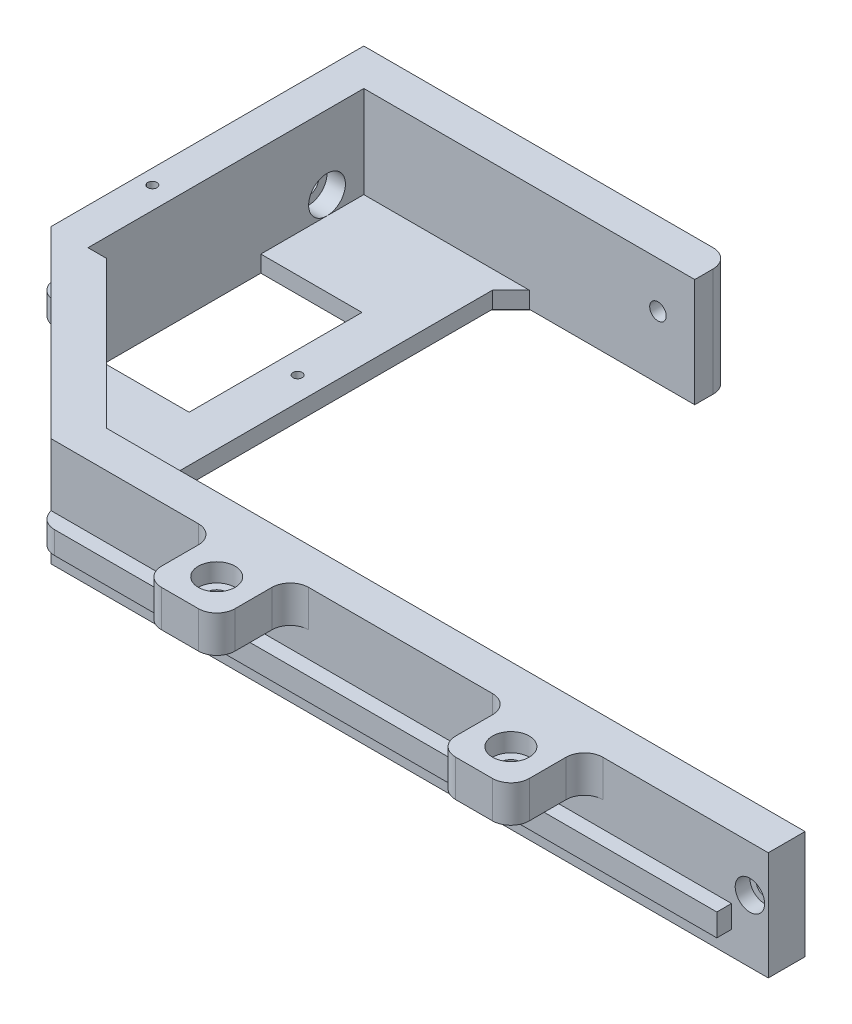
SolidWorks part; units mm, degrees
ref_plane "Front Plane" through (0, 0, 0) normal (0, 0, 1) x (1, 0, 0)
ref_plane "Top Plane" through (0, 0, 0) normal (0, 1, 0) x (1, 0, 0)
ref_plane "Right Plane" through (0, 0, 0) normal (1, 0, 0) x (0, 0, -1)
sketch "Sketch1" plane through (0, 0, 0) normal (0, 1, 0) x (1, 0, 0)
  line L0 (245, 10) -> (50, 10)
  line L1 (0, 0) -> (245, 0)
  line L2 (0, 0) -> (0, 135)
  line L3 (0, 135) -> (100, 135)
  line L4 (245, 0) -> (245, 10)
  line L5 (50, 10) -> (50, 125)
  line L6 (50, 125) -> (100, 125)
  line L7 (100, 125) -> (100, 135)
  dimension "D1" = 245
  dimension "D2" = 135
  dimension "D3" = 10
  dimension "D4" = 50
  dimension "D5" = 50
extrude "Boss-Extrude1" add sketch "Sketch1" along normal blind 30
sketch "Sketch3" plane through (0, 0, 0) normal (0, -1, 0) x (1, 0, 0)
  line L0 (50, 0) -> (0, -50)
  line L1 (0, 0) -> (245, 0) construction
  line L2 (0, -135) -> (0, 0) construction
  line L3 (0, -50) -> (0, 0)
  line L4 (0, 0) -> (50, 0)
  dimension "D1" = 45
  dimension "D2" = 50
extrude "Cut-Extrude1" cut sketch "Sketch3" against normal through all
chamfer "Chamfer1" distance 5 angle 45 2 edges at (50, 15, -125) (50, 15, -10)
sketch "Sketch4" plane through (0, 0, -135) normal (0, 0, -1) x (-1, 0, 0)
  arc A0 (-90, 15.5) -> (-90, 19.5) centre (-90, 17.5) ccw construction
  arc A1 (-90, 15.5) -> (-90, 19.5) centre (-90, 17.5) ccw
sketch "Sketch5" plane through (0, 0, 0) normal (0, 0, 1) x (1, 0, 0)
  arc A0 (240, 19.5) -> (240, 15.5) centre (240, 17.5) ccw construction
  arc A1 (90, 19.5) -> (90, 15.5) centre (90, 17.5) ccw construction
  arc A2 (240, 19.5) -> (240, 15.5) centre (240, 17.5) ccw
  arc A3 (90, 19.5) -> (90, 15.5) centre (90, 17.5) ccw
hole_wizard "CBORE for M4 SHCS2" positions "Sketch6" profile "Sketch7" counterbore size "M4" standard "ANSI Metric" end condition through all
sketch "Sketch6" plane through (0, 0, 0) normal (0, 0, 1) x (1, 0, 0)
  point P0 (240, 17.5)
  point P2 (90, 17.5)
sketch "Sketch7" plane through (240, 17.5, 0) normal (1, 0, 0) x (0, -1, 0)
  line L0 (0, 0) -> (0, 135)
  line L1 (0, 135) -> (2.25, 135)
  line L3 (2.25, 135) -> (2.25, 4)
  line L4 (2.25, 4) -> (4, 4)
  line L5 (4, 4) -> (4, 0)
  line L7 (4, 0) -> (0, 0)
  line L11 (0, -6.35) -> (0, 107.95) construction
  dimension "Thru Hole Dia." = 4.5
  dimension "Thru Hole Depth" = 135
  dimension "C'Bore Dia." = 8
  dimension "C'Bore Depth" = 4
hole_wizard "CBORE for M4 SHCS1" positions "Sketch8" profile "Sketch9" counterbore size "M4" standard "ANSI Metric" end condition through all
sketch "Sketch8" plane through (0, 0, -135) normal (0, 0, -1) x (-1, 0, 0)
  point P0 (-90, 17.5)
sketch "Sketch9" plane through (90, 17.5, -135) normal (1, 0, 0) x (0, 1, 0)
  line L0 (0, 0) -> (0, 135)
  line L1 (0, 135) -> (2.25, 135)
  line L3 (2.25, 135) -> (2.25, 4)
  line L4 (2.25, 4) -> (4, 4)
  line L5 (4, 4) -> (4, 0)
  line L7 (4, 0) -> (0, 0)
  line L11 (0, -6.35) -> (0, 107.95) construction
  dimension "Thru Hole Dia." = 4.5
  dimension "Thru Hole Depth" = 135
  dimension "C'Bore Dia." = 8
  dimension "C'Bore Depth" = 4
sketch "Sketch10" plane through (0, 30, 0) normal (0, 1, 0) x (1, 0, 0)
  line L0 (55, 125) -> (10, 125)
  line L1 (10, 125) -> (10, 55)
  line L2 (10, 55) -> (50, 15)
  line L3 (50, 15) -> (55, 125)
  line L4 (55, 10) -> (50, 15) construction
  line L5 (0, 135) -> (0, 50) construction
  dimension "D1" = 10
extrude "Cut-Extrude2" cut sketch "Sketch10" against normal offset from surface (25 mm away) 5 up to face at (86.3636, 0, -65.9091)
sketch "Sketch11" plane through (0, 30, 0) normal (0, 1, 0) x (1, 0, 0)
  line L0 (10, 125) -> (10, 55) construction
  line L1 (10, 50) -> (37.5, 50)
  line L2 (10, 50) -> (10, 97)
  line L3 (10, 97) -> (37.5, 97)
  line L4 (37.5, 50) -> (37.5, 97)
  dimension "D1" = 5
  dimension "D2" = 27.5
  dimension "D3" = 47
extrude "Cut-Extrude3" cut sketch "Sketch11" against normal through all
sketch "Sketch15" plane through (10, 0, 0) normal (1, 0, 0) x (0, 0, -1)
  line L0 (125, 10) -> (115, 10)
  line L1 (125, 5) -> (125, 30) construction
  line L2 (15, 0) -> (120, 0) construction
  dimension "D1" = 10
  dimension "D2" = 10
hole_wizard "CBORE for M5 SHCS2" positions "Sketch16" profile "Sketch17" counterbore size "M5" standard "ANSI Metric" end condition through all
sketch "Sketch16" plane through (10, 0, 0) normal (1, 0, 0) x (0, 0, -1)
  point P0 (115, 10)
sketch "Sketch17" plane through (10, 10, -115) normal (0, 1, 0) x (0, 0, -1)
  line L0 (0, 0) -> (0, 10)
  line L1 (0, 10) -> (2.75, 10)
  line L3 (2.75, 10) -> (2.75, 5)
  line L4 (2.75, 5) -> (5, 5)
  line L5 (5, 5) -> (5, 0)
  line L7 (5, 0) -> (0, 0)
  line L11 (0, -6.35) -> (0, 107.95) construction
  dimension "Thru Hole Dia." = 5.5
  dimension "Thru Hole Depth" = 10
  dimension "C'Bore Dia." = 10
  dimension "C'Bore Depth" = 5
sketch "Sketch18" plane through (0, 0, 0) normal (0, -1, 0) x (1, 0, 0)
  circle A0 centre (43.5, -73.5) radius 1.5 construction
  circle A1 centre (4, -73.5) radius 1.5 construction
  circle A2 centre (43.5, -73.5) radius 1.5
  circle A3 centre (4, -73.5) radius 1.5
hole_wizard "M3x0.5 Tapped Hole1" positions "Sketch19" profile "Sketch20" tap size "M3x0.5" standard "ANSI Metric" end condition through all
sketch "Sketch19" plane through (0, 0, 0) normal (0, -1, 0) x (-1, 0, 0)
  point P0 (-4, 73.5)
  point P3 (-43.5, 73.5)
sketch "Sketch20" plane through (4, 0, -73.5) normal (1, 0, 0) x (0, 0, -1)
  line L0 (0, 0) -> (0, 30)
  line L1 (0, 30) -> (1.25, 30)
  line L2 (1.25, 30) -> (1.25, 0)
  line L5 (1.25, 0) -> (0, 0)
  line L11 (0, -6.35) -> (0, 107.95) construction
  dimension "Thru Tap Drill Dia." = 2.5
  dimension "Thru Tap Drill Depth" = 30
cosmetic thread "Hole Thread1" parameters "D2"=3
cosmetic thread "Hole Thread2" parameters "D2"=3
sketch "Sketch21" plane through (0, 0, 0) normal (0, 0, 1) x (1, 0, 0)
  line L0 (50, 30) -> (50, 0) construction
  line L1 (50, 13.05) -> (235, 13.05)
  line L2 (50, 13.05) -> (50, 6.95)
  line L3 (50, 6.95) -> (235, 6.95)
  line L4 (235, 13.05) -> (235, 6.95)
  line L5 (245, 10) -> (235, 10) construction
  line L6 (245, 30) -> (245, 0) construction
  line L7 (50, 0) -> (245, 0) construction
  dimension "D1" = 6.1
  dimension "D2" = 10
  dimension "D3" = 10
extrude "Boss-Extrude3" add sketch "Sketch21" along normal blind 4
sketch "Sketch22" plane through (0, 0, 0) normal (-1, 0, 0) x (0, 0, 1)
  line L0 (-50, 30) -> (-50, 0) construction
  line L1 (-105, 13.05) -> (-50, 13.05)
  line L2 (-105, 13.05) -> (-105, 6.95)
  line L3 (-105, 6.95) -> (-50, 6.95)
  line L4 (-50, 13.05) -> (-50, 6.95)
  line L5 (-115, 10) -> (-105, 10) construction
  dimension "D1" = 6.1
  dimension "D2" = 10
extrude "Boss-Extrude4" add sketch "Sketch22" along normal blind 4
sketch "Sketch23" plane through (0, 30, 0) normal (0, 1, 0) x (1, 0, 0)
  line L0 (245, 10) -> (55, 10) construction
  line L1 (95, 10) -> (195, 10)
  line L2 (95, 10) -> (95, -20)
  line L3 (95, -20) -> (195, -20)
  line L4 (195, 10) -> (195, -20)
  line L5 (245, 0) -> (245, 10) construction
  dimension "D1" = 30
  dimension "D2" = 50
  dimension "D3" = 100
extrude "Boss-Extrude5" add sketch "Sketch23" against normal blind 10
sketch "Sketch24" plane through (0, 20, 0) normal (0, -1, 0) x (1, 0, 0)
  line L0 (95, 20) -> (195, 20) construction
  line L1 (115, 20) -> (175, 20)
  line L2 (115, 20) -> (115, 0)
  line L3 (115, 0) -> (175, 0)
  line L4 (175, 20) -> (175, 0)
  line L5 (95, 0) -> (195, 0) construction
  line L6 (95, 0) -> (95, 20) construction
  line L7 (195, 20) -> (195, 0) construction
  dimension "D1" = 20
  dimension "D2" = 20
extrude "Cut-Extrude4" cut sketch "Sketch24" against normal blind 10
sketch "Sketch26" plane through (0, 30, 0) normal (0, 1, 0) x (1, 0, 0)
  line L0 (95, 0) -> (115, -20) construction
  line L1 (115, -20) -> (175, -20) construction
  line L2 (175, -20) -> (195, 0) construction
hole_wizard "CBORE for M5 SHCS3" positions "Sketch31" profile "Sketch30" counterbore size "M5" standard "ANSI Metric" end condition through all
sketch "Sketch31" plane through (0, 30, 0) normal (0, 1, 0) x (1, 0, 0)
  line L0 (175, -20) -> (195, 0) construction
  line L1 (95, 0) -> (115, -20) construction
  point P0 (105, -10)
  point P2 (185, -10)
sketch "Sketch30" plane through (105, 30, 10) normal (1, 0, 0) x (0, 0, 1)
  line L0 (0, 0) -> (0, 30)
  line L1 (0, 30) -> (2.75, 30)
  line L3 (2.75, 30) -> (2.75, 5)
  line L4 (2.75, 5) -> (5, 5)
  line L5 (5, 5) -> (5, 0)
  line L7 (5, 0) -> (0, 0)
  line L11 (0, -6.35) -> (0, 107.95) construction
  dimension "Thru Hole Dia." = 5.5
  dimension "Thru Hole Depth" = 30
  dimension "C'Bore Dia." = 10
  dimension "C'Bore Depth" = 5
fillet "Fillet1" radius 5 12 edges at (-4, 10, -105) (-4, 10, -50) (50, 10, 4) (195, 25, 0) (195, 25, 20) (175, 25, 20) (175, 25, 0) (115, 25, 0) (115, 25, 20) (95, 25, 20) (95, 25, 0) (100, 15, -135)
chamfer "Chamfer2" distance 0.5 angle 45 18 edges at (0, 0, -92.5) (25, 0, -25) (147.5, 0, 0) (245, 0, -5) (150, 0, -10) (52.5, 0, -12.5) (50, 0, -67.5) (52.5, 0, -122.5) (77.5, 0, -125) (100, 0, -127.5) (98.5355, 0, -133.5355) (47.5, 0, -135) (23.75, 0, -97) (37.5, 0, -73.5) (23.75, 0, -50) (10, 0, -73.5) (43.5, 0, -74.75) (4, 0, -74.75)
